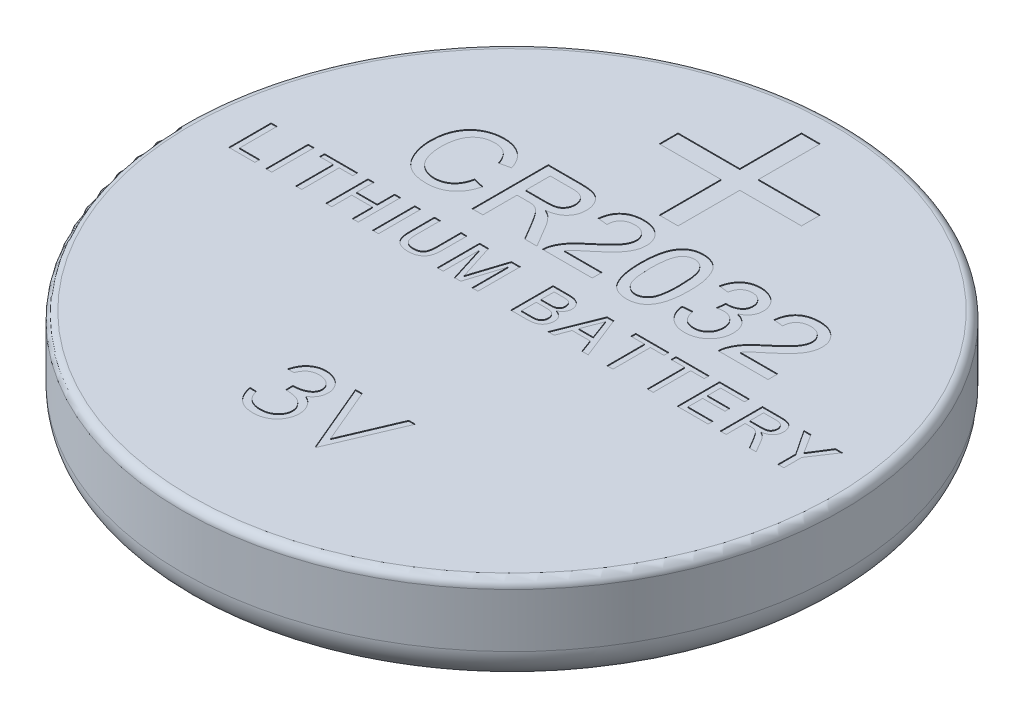
SolidWorks part; units mm, degrees
material "AISI 304"
ref_plane "Front Plane" through (0, 0, 0) normal (0, 0, 1) x (1, 0, 0)
ref_plane "Top Plane" through (0, 0, 0) normal (0, 1, 0) x (1, 0, 0)
ref_plane "Right Plane" through (0, 0, 0) normal (1, 0, 0) x (0, 0, -1)
sketch "Sketch1" plane through (0, 0, 0) normal (0, 1, 0) x (1, 0, 0)
  circle A0 centre (0, 0) radius 8.75
  dimension "D1" = 17.5
extrude "Boss-Extrude1" add sketch "Sketch1" along normal blind 3.2
sketch "Sketch7" plane through (0, 3.2, 0) normal (0, 1, 0) x (1, 0, 0)
  circle A0 centre (0, 0) radius 10
  dimension "D1" = 20
extrude "Boss-Extrude3" add sketch "Sketch7" against normal blind 2.9
sketch "Sketch3" plane through (0, 3.2, 0) normal (0, 1, 0) x (1, 0, 0)
  line L0 (0, 0) -> (0, -2.286) construction
  text T1 "+" font "Century Gothic" height in points 24
  dimension "D1" = 2.286
extrude "Cut-Extrude2" cut sketch "Sketch3" against normal blind 0.0254
fillet "Fillet3" radius 0.15 1 edges at (0, 0, 8.75)
fillet "Fillet5" radius 0.254 1 edges at (0, 3.2, 10)
fillet "Fillet4" radius 1.016 1 edges at (0, 0.3, 10)
sketch "Sketch8" plane through (0, 3.2, 0) normal (0, 1, 0) x (1, 0, 0)
  line L0 (8.0371, 2.0793) -> (-8.0371, 2.0793) construction
  text T0 "CR2032" font "Arial" height in points 9
sketch "Sketch9" plane through (0, 3.2, 0) normal (0, 1, 0) x (1, 0, 0)
  line L0 (8.89, 0) -> (-8.89, 0) construction
  text T0 "LITHIUM BATTERY" font "Arial" height in points 5
sketch "Sketch10" plane through (0, 0, 0) normal (0, -1, 0) x (-1, 0, 0)
  circle A0 centre (0, 0) radius 0.1905
  circle A1 centre (0.762, 0) radius 0.1905
  circle A2 centre (1.524, 0) radius 0.1905
  circle A3 centre (2.286, 0) radius 0.1905
  circle A4 centre (3.048, 0) radius 0.1905
  circle A5 centre (3.81, 0) radius 0.1905
  circle A6 centre (4.572, 0) radius 0.1905
  circle A7 centre (5.334, 0) radius 0.1905
  circle A8 centre (6.096, 0) radius 0.1905
  circle A9 centre (6.858, 0) radius 0.1905
  circle A10 centre (7.62, 0) radius 0.1905
  circle A11 centre (0.762, -0.762) radius 0.1905
  circle A12 centre (1.524, -0.762) radius 0.1905
  circle A13 centre (2.286, -0.762) radius 0.1905
  circle A14 centre (3.048, -0.762) radius 0.1905
  circle A15 centre (3.81, -0.762) radius 0.1905
  circle A16 centre (4.572, -0.762) radius 0.1905
  circle A17 centre (5.334, -0.762) radius 0.1905
  circle A18 centre (6.096, -0.762) radius 0.1905
  circle A19 centre (6.858, -0.762) radius 0.1905
  circle A20 centre (7.62, -0.762) radius 0.1905
  circle A21 centre (0.762, -1.524) radius 0.1905
  circle A22 centre (1.524, -1.524) radius 0.1905
  circle A23 centre (2.286, -1.524) radius 0.1905
  circle A24 centre (3.048, -1.524) radius 0.1905
  circle A25 centre (3.81, -1.524) radius 0.1905
  circle A26 centre (4.572, -1.524) radius 0.1905
  circle A27 centre (5.334, -1.524) radius 0.1905
  circle A28 centre (6.096, -1.524) radius 0.1905
  circle A29 centre (6.858, -1.524) radius 0.1905
  circle A30 centre (7.62, -1.524) radius 0.1905
  circle A31 centre (0.762, -2.286) radius 0.1905
  circle A32 centre (1.524, -2.286) radius 0.1905
  circle A33 centre (2.286, -2.286) radius 0.1905
  circle A34 centre (3.048, -2.286) radius 0.1905
  circle A35 centre (3.81, -2.286) radius 0.1905
  circle A36 centre (4.572, -2.286) radius 0.1905
  circle A37 centre (5.334, -2.286) radius 0.1905
  circle A38 centre (6.096, -2.286) radius 0.1905
  circle A39 centre (6.858, -2.286) radius 0.1905
  circle A40 centre (7.62, -2.286) radius 0.1905
  circle A41 centre (0.762, -3.048) radius 0.1905
  circle A42 centre (1.524, -3.048) radius 0.1905
  circle A43 centre (2.286, -3.048) radius 0.1905
  circle A44 centre (3.048, -3.048) radius 0.1905
  circle A45 centre (3.81, -3.048) radius 0.1905
  circle A46 centre (4.572, -3.048) radius 0.1905
  circle A47 centre (5.334, -3.048) radius 0.1905
  circle A48 centre (6.096, -3.048) radius 0.1905
  circle A49 centre (6.858, -3.048) radius 0.1905
  circle A50 centre (-0.762, 0) radius 0.1905
  circle A51 centre (0.762, -3.81) radius 0.1905
  circle A52 centre (1.524, -3.81) radius 0.1905
  circle A53 centre (2.286, -3.81) radius 0.1905
  circle A54 centre (3.048, -3.81) radius 0.1905
  circle A55 centre (3.81, -3.81) radius 0.1905
  circle A56 centre (4.572, -3.81) radius 0.1905
  circle A57 centre (5.334, -3.81) radius 0.1905
  circle A58 centre (6.096, -3.81) radius 0.1905
  circle A59 centre (6.858, -3.81) radius 0.1905
  circle A60 centre (-0.762, -0.762) radius 0.1905
  circle A61 centre (0.762, -4.572) radius 0.1905
  circle A62 centre (1.524, -4.572) radius 0.1905
  circle A63 centre (2.286, -4.572) radius 0.1905
  circle A64 centre (3.048, -4.572) radius 0.1905
  circle A65 centre (3.81, -4.572) radius 0.1905
  circle A66 centre (4.572, -4.572) radius 0.1905
  circle A67 centre (5.334, -4.572) radius 0.1905
  circle A68 centre (6.096, -4.572) radius 0.1905
  circle A69 centre (-0.762, -1.524) radius 0.1905
  circle A70 centre (-0.762, -2.286) radius 0.1905
  circle A71 centre (0.762, -5.334) radius 0.1905
  circle A72 centre (1.524, -5.334) radius 0.1905
  circle A73 centre (2.286, -5.334) radius 0.1905
  circle A74 centre (3.048, -5.334) radius 0.1905
  circle A75 centre (3.81, -5.334) radius 0.1905
  circle A76 centre (4.572, -5.334) radius 0.1905
  circle A77 centre (5.334, -5.334) radius 0.1905
  circle A78 centre (-0.762, -3.048) radius 0.1905
  circle A79 centre (-0.762, -3.81) radius 0.1905
  circle A80 centre (-0.762, -4.572) radius 0.1905
  circle A81 centre (0.762, -6.096) radius 0.1905
  circle A82 centre (1.524, -6.096) radius 0.1905
  circle A83 centre (2.286, -6.096) radius 0.1905
  circle A84 centre (3.048, -6.096) radius 0.1905
  circle A85 centre (3.81, -6.096) radius 0.1905
  circle A86 centre (4.572, -6.096) radius 0.1905
  circle A87 centre (-0.762, -5.334) radius 0.1905
  circle A88 centre (-0.762, -6.096) radius 0.1905
  circle A89 centre (-0.762, -6.858) radius 0.1905
  circle A90 centre (-0.762, -7.62) radius 0.1905
  circle A91 centre (0.762, -6.858) radius 0.1905
  circle A92 centre (1.524, -6.858) radius 0.1905
  circle A93 centre (2.286, -6.858) radius 0.1905
  circle A94 centre (3.048, -6.858) radius 0.1905
  circle A95 centre (3.81, -6.858) radius 0.1905
  circle A96 centre (-1.524, 0) radius 0.1905
  circle A97 centre (-1.524, -0.762) radius 0.1905
  circle A98 centre (-1.524, -1.524) radius 0.1905
  circle A99 centre (-1.524, -2.286) radius 0.1905
  circle A100 centre (-1.524, -3.048) radius 0.1905
  circle A101 centre (0.762, -7.62) radius 0.1905
  circle A102 centre (1.524, -7.62) radius 0.1905
  circle A103 centre (2.286, -7.62) radius 0.1905
  circle A104 centre (-1.524, -3.81) radius 0.1905
  circle A105 centre (-1.524, -4.572) radius 0.1905
  circle A106 centre (-1.524, -5.334) radius 0.1905
  circle A107 centre (-1.524, -6.096) radius 0.1905
  circle A108 centre (-1.524, -6.858) radius 0.1905
  circle A109 centre (-1.524, -7.62) radius 0.1905
  circle A110 centre (-2.286, 0) radius 0.1905
  circle A111 centre (0, -0.762) radius 0.1905
  circle A112 centre (0, -1.524) radius 0.1905
  circle A113 centre (0, -2.286) radius 0.1905
  circle A114 centre (0, -3.048) radius 0.1905
  circle A115 centre (0, -3.81) radius 0.1905
  circle A116 centre (0, -4.572) radius 0.1905
  circle A117 centre (0, -5.334) radius 0.1905
  circle A118 centre (0, -6.096) radius 0.1905
  circle A119 centre (0, -6.858) radius 0.1905
  circle A120 centre (0, -7.62) radius 0.1905
  circle A121 centre (7.62, -7.62) radius 0.1905 [skipped]
  circle A122 centre (6.858, -7.62) radius 0.1905 [skipped]
  circle A123 centre (7.62, -6.858) radius 0.1905 [skipped]
  circle A124 centre (7.62, -6.096) radius 0.1905 [skipped]
  circle A125 centre (6.858, -6.858) radius 0.1905 [skipped]
  circle A126 centre (6.096, -7.62) radius 0.1905 [skipped]
  circle A127 centre (6.096, -6.858) radius 0.1905 [skipped]
  circle A128 centre (5.334, -7.62) radius 0.1905 [skipped]
  circle A129 centre (4.572, -7.62) radius 0.1905 [skipped]
  circle A130 centre (3.81, -7.62) radius 0.1905 [skipped]
  circle A131 centre (5.334, -6.858) radius 0.1905 [skipped]
  circle A132 centre (6.096, -6.096) radius 0.1905 [skipped]
  circle A133 centre (6.858, -6.096) radius 0.1905 [skipped]
  circle A134 centre (6.858, -5.334) radius 0.1905 [skipped]
  circle A135 centre (7.62, -5.334) radius 0.1905 [skipped]
  circle A136 centre (7.62, -4.572) radius 0.1905 [skipped]
  circle A137 centre (7.62, -3.81) radius 0.1905 [skipped]
  circle A138 centre (6.858, -4.572) radius 0.1905 [skipped]
  circle A139 centre (7.62, -3.048) radius 0.1905 [skipped]
  circle A140 centre (6.096, -5.334) radius 0.1905 [skipped]
  circle A141 centre (5.334, -6.096) radius 0.1905 [skipped]
  circle A142 centre (4.572, -6.858) radius 0.1905 [skipped]
  circle A143 centre (3.048, -7.62) radius 0.1905 [skipped]
  circle A144 centre (-2.286, -0.762) radius 0.1905
  circle A145 centre (-2.286, -1.524) radius 0.1905
  circle A146 centre (-2.286, -2.286) radius 0.1905
  circle A147 centre (-2.286, -3.048) radius 0.1905
  circle A148 centre (-2.286, -3.81) radius 0.1905
  circle A149 centre (-2.286, -4.572) radius 0.1905
  circle A150 centre (-2.286, -5.334) radius 0.1905
  circle A151 centre (-2.286, -6.096) radius 0.1905
  circle A152 centre (-2.286, -6.858) radius 0.1905
  circle A153 centre (-2.286, -7.62) radius 0.1905
  circle A154 centre (-3.048, 0) radius 0.1905
  circle A155 centre (-3.048, -0.762) radius 0.1905
  circle A156 centre (-3.048, -1.524) radius 0.1905
  circle A157 centre (-3.048, -2.286) radius 0.1905
  circle A158 centre (-3.048, -3.048) radius 0.1905
  circle A159 centre (-3.048, -3.81) radius 0.1905
  circle A160 centre (-3.048, -4.572) radius 0.1905
  circle A161 centre (-3.048, -5.334) radius 0.1905
  circle A162 centre (-3.048, -6.096) radius 0.1905
  circle A163 centre (-3.048, -6.858) radius 0.1905
  circle A164 centre (0, 0.762) radius 0.1905
  circle A165 centre (-3.81, 0) radius 0.1905
  circle A166 centre (-3.81, -0.762) radius 0.1905
  circle A167 centre (-3.81, -1.524) radius 0.1905
  circle A168 centre (-3.81, -2.286) radius 0.1905
  circle A169 centre (-3.81, -3.048) radius 0.1905
  circle A170 centre (-3.81, -3.81) radius 0.1905
  circle A171 centre (-3.81, -4.572) radius 0.1905
  circle A172 centre (-3.81, -5.334) radius 0.1905
  circle A173 centre (-3.81, -6.096) radius 0.1905
  circle A174 centre (-3.81, -6.858) radius 0.1905
  circle A175 centre (0.762, 0.762) radius 0.1905
  circle A176 centre (-4.572, 0) radius 0.1905
  circle A177 centre (-4.572, -0.762) radius 0.1905
  circle A178 centre (-4.572, -1.524) radius 0.1905
  circle A179 centre (-4.572, -2.286) radius 0.1905
  circle A180 centre (-4.572, -3.048) radius 0.1905
  circle A181 centre (-4.572, -3.81) radius 0.1905
  circle A182 centre (-4.572, -4.572) radius 0.1905
  circle A183 centre (-4.572, -5.334) radius 0.1905
  circle A184 centre (-4.572, -6.096) radius 0.1905
  circle A185 centre (1.524, 0.762) radius 0.1905
  circle A186 centre (2.286, 0.762) radius 0.1905
  circle A187 centre (-5.334, 0) radius 0.1905
  circle A188 centre (-5.334, -0.762) radius 0.1905
  circle A189 centre (-5.334, -1.524) radius 0.1905
  circle A190 centre (-5.334, -2.286) radius 0.1905
  circle A191 centre (-5.334, -3.048) radius 0.1905
  circle A192 centre (-5.334, -3.81) radius 0.1905
  circle A193 centre (-5.334, -4.572) radius 0.1905
  circle A194 centre (-5.334, -5.334) radius 0.1905
  circle A195 centre (3.048, 0.762) radius 0.1905
  circle A196 centre (3.81, 0.762) radius 0.1905
  circle A197 centre (4.572, 0.762) radius 0.1905
  circle A198 centre (-6.096, 0) radius 0.1905
  circle A199 centre (-6.096, -0.762) radius 0.1905
  circle A200 centre (-6.096, -1.524) radius 0.1905
  circle A201 centre (-6.096, -2.286) radius 0.1905
  circle A202 centre (-6.096, -3.048) radius 0.1905
  circle A203 centre (-6.096, -3.81) radius 0.1905
  circle A204 centre (-6.096, -4.572) radius 0.1905
  circle A205 centre (5.334, 0.762) radius 0.1905
  circle A206 centre (6.096, 0.762) radius 0.1905
  circle A207 centre (6.858, 0.762) radius 0.1905
  circle A208 centre (7.62, 0.762) radius 0.1905
  circle A209 centre (-6.858, 0) radius 0.1905
  circle A210 centre (-6.858, -0.762) radius 0.1905
  circle A211 centre (-6.858, -1.524) radius 0.1905
  circle A212 centre (-6.858, -2.286) radius 0.1905
  circle A213 centre (-6.858, -3.048) radius 0.1905
  circle A214 centre (-6.858, -3.81) radius 0.1905
  circle A215 centre (-0.762, 0.762) radius 0.1905
  circle A216 centre (-1.524, 0.762) radius 0.1905
  circle A217 centre (-2.286, 0.762) radius 0.1905
  circle A218 centre (-3.048, 0.762) radius 0.1905
  circle A219 centre (-3.81, 0.762) radius 0.1905
  circle A220 centre (-7.62, 0) radius 0.1905
  circle A221 centre (-7.62, -0.762) radius 0.1905
  circle A222 centre (-7.62, -1.524) radius 0.1905
  circle A223 centre (-7.62, -2.286) radius 0.1905
  circle A224 centre (-4.572, 0.762) radius 0.1905
  circle A225 centre (-5.334, 0.762) radius 0.1905
  circle A226 centre (-6.096, 0.762) radius 0.1905
  circle A227 centre (-6.858, 0.762) radius 0.1905
  circle A228 centre (-7.62, 0.762) radius 0.1905
  circle A229 centre (0, 1.524) radius 0.1905
  circle A230 centre (0.762, 1.524) radius 0.1905
  circle A231 centre (-7.62, -7.62) radius 0.1905 [skipped]
  circle A232 centre (-7.62, -6.858) radius 0.1905 [skipped]
  circle A233 centre (-6.858, -7.62) radius 0.1905 [skipped]
  circle A234 centre (-7.62, -6.096) radius 0.1905 [skipped]
  circle A235 centre (-7.62, -5.334) radius 0.1905 [skipped]
  circle A236 centre (-7.62, -4.572) radius 0.1905 [skipped]
  circle A237 centre (-6.858, -5.334) radius 0.1905 [skipped]
  circle A238 centre (-6.858, -6.096) radius 0.1905 [skipped]
  circle A239 centre (-6.858, -6.858) radius 0.1905 [skipped]
  circle A240 centre (-6.096, -6.858) radius 0.1905 [skipped]
  circle A241 centre (-6.096, -7.62) radius 0.1905 [skipped]
  circle A242 centre (-5.334, -7.62) radius 0.1905 [skipped]
  circle A243 centre (-4.572, -7.62) radius 0.1905 [skipped]
  circle A244 centre (-3.81, -7.62) radius 0.1905 [skipped]
  circle A245 centre (-5.334, -6.858) radius 0.1905 [skipped]
  circle A246 centre (-6.096, -6.096) radius 0.1905 [skipped]
  circle A247 centre (-7.62, -3.81) radius 0.1905 [skipped]
  circle A248 centre (-6.858, -4.572) radius 0.1905 [skipped]
  circle A249 centre (-7.62, -3.048) radius 0.1905 [skipped]
  circle A250 centre (-6.096, -5.334) radius 0.1905 [skipped]
  circle A251 centre (-5.334, -6.096) radius 0.1905 [skipped]
  circle A252 centre (-4.572, -6.858) radius 0.1905 [skipped]
  circle A253 centre (-3.048, -7.62) radius 0.1905 [skipped]
  circle A254 centre (1.524, 1.524) radius 0.1905
  circle A255 centre (2.286, 1.524) radius 0.1905
  circle A256 centre (3.048, 1.524) radius 0.1905
  circle A257 centre (3.81, 1.524) radius 0.1905
  circle A258 centre (4.572, 1.524) radius 0.1905
  circle A259 centre (5.334, 1.524) radius 0.1905
  circle A260 centre (6.096, 1.524) radius 0.1905
  circle A261 centre (6.858, 1.524) radius 0.1905
  circle A262 centre (7.62, 1.524) radius 0.1905
  circle A263 centre (-0.762, 1.524) radius 0.1905
  circle A264 centre (-1.524, 1.524) radius 0.1905
  circle A265 centre (-2.286, 1.524) radius 0.1905
  circle A266 centre (-3.048, 1.524) radius 0.1905
  circle A267 centre (-3.81, 1.524) radius 0.1905
  circle A268 centre (-4.572, 1.524) radius 0.1905
  circle A269 centre (-5.334, 1.524) radius 0.1905
  circle A270 centre (-6.096, 1.524) radius 0.1905
  circle A271 centre (-6.858, 1.524) radius 0.1905
  circle A272 centre (-7.62, 1.524) radius 0.1905
  circle A273 centre (0, 2.286) radius 0.1905
  circle A274 centre (0.762, 2.286) radius 0.1905
  circle A275 centre (1.524, 2.286) radius 0.1905
  circle A276 centre (2.286, 2.286) radius 0.1905
  circle A277 centre (3.048, 2.286) radius 0.1905
  circle A278 centre (3.81, 2.286) radius 0.1905
  circle A279 centre (4.572, 2.286) radius 0.1905
  circle A280 centre (5.334, 2.286) radius 0.1905
  circle A281 centre (6.096, 2.286) radius 0.1905
  circle A282 centre (6.858, 2.286) radius 0.1905
  circle A283 centre (7.62, 2.286) radius 0.1905
  circle A284 centre (-0.762, 2.286) radius 0.1905
  circle A285 centre (-1.524, 2.286) radius 0.1905
  circle A286 centre (-2.286, 2.286) radius 0.1905
  circle A287 centre (-3.048, 2.286) radius 0.1905
  circle A288 centre (-3.81, 2.286) radius 0.1905
  circle A289 centre (-4.572, 2.286) radius 0.1905
  circle A290 centre (-5.334, 2.286) radius 0.1905
  circle A291 centre (-6.096, 2.286) radius 0.1905
  circle A292 centre (-6.858, 2.286) radius 0.1905
  circle A293 centre (-7.62, 2.286) radius 0.1905
  circle A294 centre (0, 3.048) radius 0.1905
  circle A295 centre (0.762, 3.048) radius 0.1905
  circle A296 centre (1.524, 3.048) radius 0.1905
  circle A297 centre (2.286, 3.048) radius 0.1905
  circle A298 centre (3.048, 3.048) radius 0.1905
  circle A299 centre (3.81, 3.048) radius 0.1905
  circle A300 centre (4.572, 3.048) radius 0.1905
  circle A301 centre (5.334, 3.048) radius 0.1905
  circle A302 centre (6.096, 3.048) radius 0.1905
  circle A303 centre (6.858, 3.048) radius 0.1905
  circle A305 centre (-0.762, 3.048) radius 0.1905
  circle A306 centre (-1.524, 3.048) radius 0.1905
  circle A307 centre (-2.286, 3.048) radius 0.1905
  circle A308 centre (-3.048, 3.048) radius 0.1905
  circle A309 centre (-3.81, 3.048) radius 0.1905
  circle A310 centre (-4.572, 3.048) radius 0.1905
  circle A311 centre (-5.334, 3.048) radius 0.1905
  circle A312 centre (-6.096, 3.048) radius 0.1905
  circle A313 centre (-6.858, 3.048) radius 0.1905
  circle A315 centre (0, 3.81) radius 0.1905
  circle A316 centre (0.762, 3.81) radius 0.1905
  circle A317 centre (1.524, 3.81) radius 0.1905
  circle A318 centre (2.286, 3.81) radius 0.1905
  circle A319 centre (3.048, 3.81) radius 0.1905
  circle A320 centre (3.81, 3.81) radius 0.1905
  circle A321 centre (4.572, 3.81) radius 0.1905
  circle A322 centre (5.334, 3.81) radius 0.1905
  circle A323 centre (6.096, 3.81) radius 0.1905
  circle A324 centre (6.858, 3.81) radius 0.1905
  circle A326 centre (-0.762, 3.81) radius 0.1905
  circle A327 centre (-1.524, 3.81) radius 0.1905
  circle A328 centre (-2.286, 3.81) radius 0.1905
  circle A329 centre (-3.048, 3.81) radius 0.1905
  circle A330 centre (-3.81, 3.81) radius 0.1905
  circle A331 centre (-4.572, 3.81) radius 0.1905
  circle A332 centre (-5.334, 3.81) radius 0.1905
  circle A333 centre (-6.096, 3.81) radius 0.1905
  circle A334 centre (-6.858, 3.81) radius 0.1905
  circle A336 centre (0, 4.572) radius 0.1905
  circle A337 centre (0.762, 4.572) radius 0.1905
  circle A338 centre (1.524, 4.572) radius 0.1905
  circle A339 centre (2.286, 4.572) radius 0.1905
  circle A340 centre (3.048, 4.572) radius 0.1905
  circle A341 centre (3.81, 4.572) radius 0.1905
  circle A342 centre (4.572, 4.572) radius 0.1905
  circle A343 centre (5.334, 4.572) radius 0.1905
  circle A344 centre (6.096, 4.572) radius 0.1905
  circle A347 centre (-0.762, 4.572) radius 0.1905
  circle A348 centre (-1.524, 4.572) radius 0.1905
  circle A349 centre (-2.286, 4.572) radius 0.1905
  circle A350 centre (-3.048, 4.572) radius 0.1905
  circle A351 centre (-3.81, 4.572) radius 0.1905
  circle A352 centre (-4.572, 4.572) radius 0.1905
  circle A353 centre (-5.334, 4.572) radius 0.1905
  circle A354 centre (-6.096, 4.572) radius 0.1905
  circle A357 centre (0, 5.334) radius 0.1905
  circle A358 centre (0.762, 5.334) radius 0.1905
  circle A359 centre (1.524, 5.334) radius 0.1905
  circle A360 centre (2.286, 5.334) radius 0.1905
  circle A361 centre (3.048, 5.334) radius 0.1905
  circle A362 centre (3.81, 5.334) radius 0.1905
  circle A363 centre (4.572, 5.334) radius 0.1905
  circle A364 centre (5.334, 5.334) radius 0.1905
  circle A368 centre (-0.762, 5.334) radius 0.1905
  circle A369 centre (-1.524, 5.334) radius 0.1905
  circle A370 centre (-2.286, 5.334) radius 0.1905
  circle A371 centre (-3.048, 5.334) radius 0.1905
  circle A372 centre (-3.81, 5.334) radius 0.1905
  circle A373 centre (-4.572, 5.334) radius 0.1905
  circle A374 centre (-5.334, 5.334) radius 0.1905
  circle A378 centre (0, 6.096) radius 0.1905
  circle A379 centre (0.762, 6.096) radius 0.1905
  circle A380 centre (1.524, 6.096) radius 0.1905
  circle A381 centre (2.286, 6.096) radius 0.1905
  circle A382 centre (3.048, 6.096) radius 0.1905
  circle A383 centre (3.81, 6.096) radius 0.1905
  circle A384 centre (4.572, 6.096) radius 0.1905
  circle A389 centre (-0.762, 6.096) radius 0.1905
  circle A390 centre (-1.524, 6.096) radius 0.1905
  circle A391 centre (-2.286, 6.096) radius 0.1905
  circle A392 centre (-3.048, 6.096) radius 0.1905
  circle A393 centre (-3.81, 6.096) radius 0.1905
  circle A394 centre (-4.572, 6.096) radius 0.1905
  circle A399 centre (0, 6.858) radius 0.1905
  circle A400 centre (0.762, 6.858) radius 0.1905
  circle A401 centre (1.524, 6.858) radius 0.1905
  circle A402 centre (2.286, 6.858) radius 0.1905
  circle A403 centre (3.048, 6.858) radius 0.1905
  circle A404 centre (3.81, 6.858) radius 0.1905
  circle A410 centre (-0.762, 6.858) radius 0.1905
  circle A411 centre (-1.524, 6.858) radius 0.1905
  circle A412 centre (-2.286, 6.858) radius 0.1905
  circle A413 centre (-3.048, 6.858) radius 0.1905
  circle A414 centre (-3.81, 6.858) radius 0.1905
  circle A420 centre (0, 7.62) radius 0.1905
  circle A421 centre (0.762, 7.62) radius 0.1905
  circle A422 centre (1.524, 7.62) radius 0.1905
  circle A423 centre (2.286, 7.62) radius 0.1905
  circle A431 centre (-0.762, 7.62) radius 0.1905
  circle A432 centre (-1.524, 7.62) radius 0.1905
  circle A433 centre (-2.286, 7.62) radius 0.1905
  circle A441 centre (-7.62, 7.62) radius 0.1905 [skipped]
  circle A442 centre (-6.858, 7.62) radius 0.1905 [skipped]
  circle A443 centre (-7.62, 6.858) radius 0.1905 [skipped]
  circle A444 centre (-6.858, 6.858) radius 0.1905 [skipped]
  circle A445 centre (-6.096, 7.62) radius 0.1905 [skipped]
  circle A446 centre (-5.334, 7.62) radius 0.1905 [skipped]
  circle A447 centre (-6.096, 6.858) radius 0.1905 [skipped]
  circle A448 centre (-6.858, 6.096) radius 0.1905 [skipped]
  circle A449 centre (-7.62, 5.334) radius 0.1905 [skipped]
  circle A450 centre (-7.62, 6.096) radius 0.1905 [skipped]
  circle A451 centre (-7.62, 4.572) radius 0.1905 [skipped]
  circle A452 centre (-6.858, 5.334) radius 0.1905 [skipped]
  circle A453 centre (-6.096, 6.096) radius 0.1905 [skipped]
  circle A454 centre (-5.334, 6.858) radius 0.1905 [skipped]
  circle A455 centre (-4.572, 7.62) radius 0.1905 [skipped]
  circle A456 centre (-3.81, 7.62) radius 0.1905 [skipped]
  circle A457 centre (-7.62, 3.81) radius 0.1905 [skipped]
  circle A458 centre (7.62, 7.62) radius 0.1905 [skipped]
  circle A459 centre (6.858, 7.62) radius 0.1905 [skipped]
  circle A460 centre (7.62, 6.858) radius 0.1905 [skipped]
  circle A461 centre (6.096, 7.62) radius 0.1905 [skipped]
  circle A462 centre (6.858, 6.858) radius 0.1905 [skipped]
  circle A463 centre (7.62, 6.096) radius 0.1905 [skipped]
  circle A464 centre (5.334, 7.62) radius 0.1905 [skipped]
  circle A465 centre (6.096, 6.858) radius 0.1905 [skipped]
  circle A466 centre (6.858, 6.096) radius 0.1905 [skipped]
  circle A467 centre (7.62, 5.334) radius 0.1905 [skipped]
  circle A468 centre (7.62, 4.572) radius 0.1905 [skipped]
  circle A469 centre (7.62, 3.81) radius 0.1905 [skipped]
  circle A470 centre (6.858, 5.334) radius 0.1905 [skipped]
  circle A471 centre (6.096, 6.096) radius 0.1905 [skipped]
  circle A472 centre (5.334, 6.858) radius 0.1905 [skipped]
  circle A473 centre (4.572, 7.62) radius 0.1905 [skipped]
  circle A474 centre (3.81, 7.62) radius 0.1905 [skipped]
  circle A475 centre (-3.048, 7.62) radius 0.1905 [skipped]
  circle A476 centre (3.048, 7.62) radius 0.1905 [skipped]
  circle A477 centre (7.62, 3.048) radius 0.1905 [skipped]
  circle A478 centre (-7.62, 3.048) radius 0.1905 [skipped]
  circle A479 centre (-6.858, 4.572) radius 0.1905 [skipped]
  circle A480 centre (6.858, 4.572) radius 0.1905 [skipped]
  circle A481 centre (6.096, 5.334) radius 0.1905 [skipped]
  circle A482 centre (5.334, 6.096) radius 0.1905 [skipped]
  circle A483 centre (4.572, 6.858) radius 0.1905 [skipped]
  circle A484 centre (-4.572, 6.858) radius 0.1905 [skipped]
  circle A485 centre (-5.334, 6.096) radius 0.1905 [skipped]
  circle A486 centre (-6.096, 5.334) radius 0.1905 [skipped]
  dimension "D1" = 0.381
  dimension "D4" = 0.762
  dimension "D2" = 11
  dimension "D3" = 11
  dimension "D5" = 11
  dimension "D6" = 11
wrap "Wrap1" sketch "Sketch10" wrap type scribe source sketch "Sketch10" face at (0, 0, 8.6)
extrude "Cut-Extrude5" cut sketch "Sketch8" against normal blind 0.0254
extrude "Cut-Extrude6" cut sketch "Sketch9" against normal blind 0.0254
sketch "Sketch15" plane through (0, 3.2, 0) normal (0, 1, 0) x (1, 0, 0)
  line L1 (4.5425, -6.5601) -> (-4.9603, -6.5601) construction
  text T0 "3V" font "Century Gothic" height in points 8
extrude "Cut-Extrude7" cut sketch "Sketch15" against normal blind 0.0254
